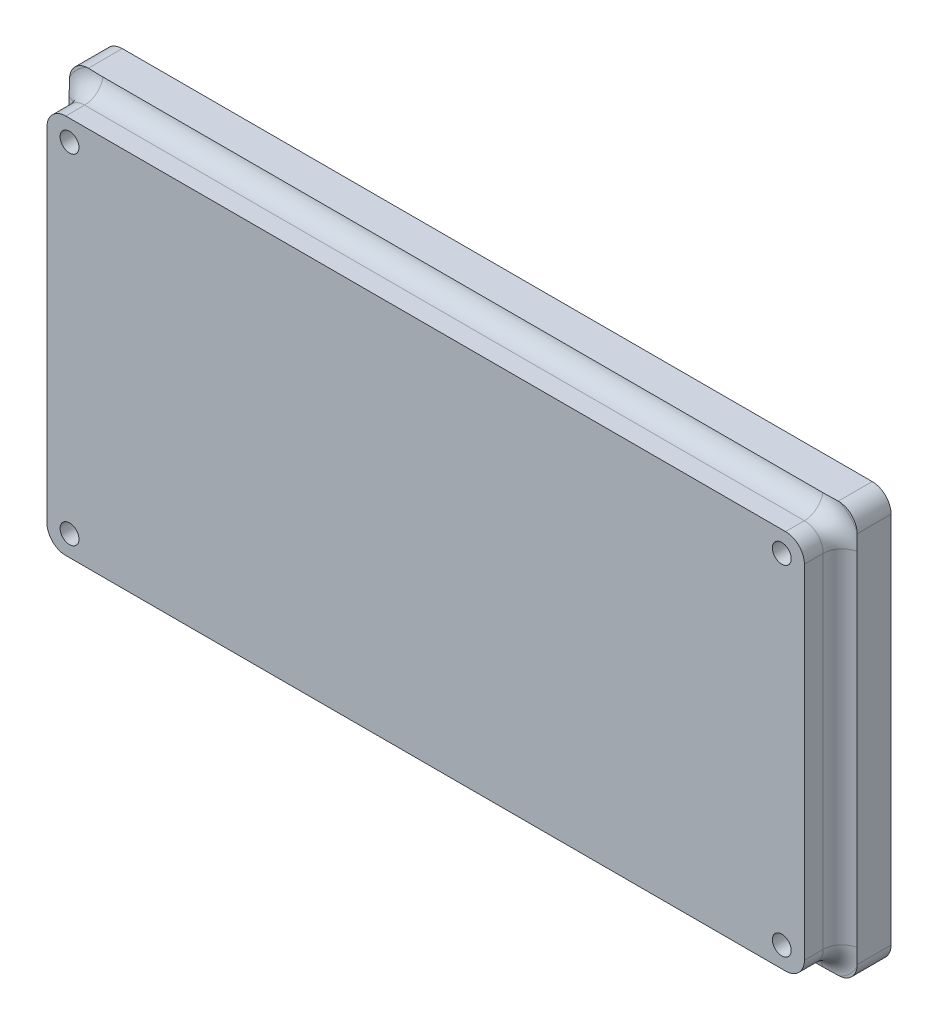
SolidWorks part; units mm, degrees
ref_plane "Plano frontal" through (0, 0, 0) normal (0, 0, 1) x (1, 0, 0)
ref_plane "Plano superior" through (0, 0, 0) normal (0, 1, 0) x (1, 0, 0)
ref_plane "Plano direito" through (0, 0, 0) normal (1, 0, 0) x (0, 0, -1)
sketch "Esboço1" plane through (0, 0, 0) normal (0, 0, 1) x (1, 0, 0)
  line L1 (-104.5, 54.5) -> (104.5, 54.5)
  line L2 (-104.5, 54.5) -> (-104.5, -54.5)
  line L3 (-104.5, -54.5) -> (104.5, -54.5)
  line L4 (104.5, 54.5) -> (104.5, -54.5)
  line L5 (-104.5, 54.5) -> (104.5, -54.5) construction
  line L6 (-104.5, -54.5) -> (104.5, 54.5) construction
  point P0 (0, 0)
  dimension "D1" = 209
  dimension "D2" = 109
extrude "Ressalto-extrusão2" add sketch "Esboço1" along normal blind 19
fillet "Filete2" radius 5 4 edges at (-104.5, 54.5, 9.5) (-104.5, -54.5, 9.5) (104.5, -54.5, 9.5) (104.5, 54.5, 9.5)
ref_plane "Plano Posterior" through (0, 0, 19) normal (0, 0, 1) x (1, 0, 0)
sketch "Esboço12" plane through (0, 0, 19) normal (0, 0, 1) x (1, 0, 0)
  line L1 (-100.5, 50.5) -> (100.5, 50.5)
  line L2 (-100.5, 50.5) -> (-100.5, -50.5)
  line L3 (-100.5, -50.5) -> (100.5, -50.5)
  line L4 (100.5, 50.5) -> (100.5, -50.5)
  line L5 (-100.5, 50.5) -> (100.5, -50.5) construction
  line L6 (-100.5, -50.5) -> (100.5, 50.5) construction
  point P0 (0, 0)
  dimension "D1" = 201
  dimension "D2" = 101
extrude "Corte-extrusão8" cut sketch "Esboço12" against normal blind 10 flip side to cut
fillet "Filete3" radius 5 4 edges at (100.5, -50.5, 14) (-100.5, -50.5, 14) (-100.5, 50.5, 14) (100.5, 50.5, 14)
fillet "Filete4" radius 5 4 edges at (-99.0355, 49.0355, 9) (99.0355, 49.0355, 9) (99.0355, -49.0355, 9) (-99.0355, -49.0355, 9)
sketch "Esboço14" plane through (0, 0, 0) normal (0, 0, 1) x (1, 0, 0)
  line L0 (97.5, -36.5) -> (90.5, -36.5)
  line L1 (97.5, 48.5) -> (-97.5, 48.5) construction
  line L2 (97.5, 48.5) -> (97.5, -48.5) construction
  line L3 (97.5, -48.5) -> (-97.5, -48.5) construction
  line L4 (-97.5, 48.5) -> (-97.5, -48.5) construction
  line L5 (97.5, 48.5) -> (-97.5, -48.5) construction
  line L6 (97.5, -48.5) -> (-97.5, 48.5) construction
  line L7 (85.5, -41.5) -> (85.5, -48.5)
  line L8 (0, 0) -> (-97.5, 0) construction
  line L9 (0, 0) -> (97.5, 0) construction
  line L10 (97.5, 36.5) -> (97.5, -36.5)
  line L11 (85.5, -48.5) -> (-85.5, -48.5)
  line L12 (85.5, 48.5) -> (-85.5, 48.5)
  line L13 (85.5, 41.5) -> (85.5, 48.5)
  line L14 (97.5, 36.5) -> (90.5, 36.5)
  line L15 (0, -48.5) -> (0, 48.5) construction
  line L16 (-85.5, 41.5) -> (-85.5, 48.5)
  line L17 (-97.5, 36.5) -> (-90.5, 36.5)
  line L18 (-97.5, 36.5) -> (-97.5, -36.5)
  line L19 (-97.5, -36.5) -> (-90.5, -36.5)
  line L20 (-85.5, -41.5) -> (-85.5, -48.5)
  arc A0 (85.5, -41.5) -> (90.5, -36.5) centre (90.5, -41.5) cw
  arc A1 (85.5, 41.5) -> (90.5, 36.5) centre (90.5, 41.5) ccw
  arc A2 (-85.5, 41.5) -> (-90.5, 36.5) centre (-90.5, 41.5) cw
  arc A3 (-85.5, -41.5) -> (-90.5, -36.5) centre (-90.5, -41.5) ccw
  point P0 (0, 0)
  point P11 (85.5, -36.5)
  dimension "D5" = 5
  dimension "D1" = 195
  dimension "D2" = 97
  dimension "D3" = 12
  dimension "D4" = 12
extrude "Corte-extrusão9" cut sketch "Esboço14" along normal blind 16
sketch "Esboço16" plane through (0, 0, 0) normal (0, 0, 1) x (1, 0, 0)
  line L0 (99.5, -38) -> (92.5, -38)
  line L1 (99.5, 50) -> (-99.5, 50) construction
  line L2 (99.5, 50) -> (99.5, -50) construction
  line L3 (99.5, -50) -> (-99.5, -50) construction
  line L4 (-99.5, 50) -> (-99.5, -50) construction
  line L5 (99.5, 50) -> (-99.5, -50) construction
  line L6 (99.5, -50) -> (-99.5, 50) construction
  line L7 (87.5, -43) -> (87.5, -50)
  line L8 (0, 0) -> (-99.5, 0) construction
  line L9 (0, 0) -> (99.5, 0) construction
  line L10 (99.5, 38) -> (99.5, -38)
  line L11 (87.5, -50) -> (-87.5, -50)
  line L12 (87.5, 50) -> (-87.5, 50)
  line L13 (87.5, 43) -> (87.5, 50)
  line L14 (99.5, 38) -> (92.5, 38)
  line L15 (0, -50) -> (0, 50) construction
  line L16 (-87.5, 43) -> (-87.5, 50)
  line L17 (-99.5, 38) -> (-92.5, 38)
  line L18 (-99.5, 38) -> (-99.5, -38)
  line L19 (-99.5, -38) -> (-92.5, -38)
  line L20 (-87.5, -43) -> (-87.5, -50)
  line L21 (0, 0) -> (-97.5, 0) construction
  line L22 (0, -48.5) -> (0, 48.5) construction
  line L24 (97.5, 52.5) -> (-97.5, 52.5)
  line L25 (102.5, 47.5) -> (102.5, -47.5)
  line L26 (97.5, -52.5) -> (-97.5, -52.5)
  line L27 (-102.5, 47.5) -> (-102.5, -47.5)
  line L28 (102.5, 52.5) -> (-102.5, -52.5) construction
  line L29 (102.5, -52.5) -> (-102.5, 52.5) construction
  arc A0 (87.5, -43) -> (92.5, -38) centre (92.5, -43) cw
  arc A1 (87.5, 43) -> (92.5, 38) centre (92.5, 43) ccw
  arc A2 (-87.5, 43) -> (-92.5, 38) centre (-92.5, 43) cw
  arc A3 (-87.5, -43) -> (-92.5, -38) centre (-92.5, -43) ccw
  arc A4 (-97.5, 52.5) -> (-102.5, 47.5) centre (-97.5, 47.5) ccw
  arc A5 (-102.5, -47.5) -> (-97.5, -52.5) centre (-97.5, -47.5) ccw
  arc A6 (97.5, -52.5) -> (102.5, -47.5) centre (97.5, -47.5) ccw
  arc A7 (97.5, 52.5) -> (102.5, 47.5) centre (97.5, 47.5) cw
  point P0 (0, 0)
  point P11 (87.5, -38)
  dimension "D5" = 5
  dimension "D8" = 5
  dimension "D1" = 199
  dimension "D2" = 100
  dimension "D3" = 12
  dimension "D4" = 12
  dimension "D6" = 205
  dimension "D7" = 105
extrude "Corte-extrusão10" cut sketch "Esboço16" along normal blind 3
sketch "Esboço17" plane through (0, 0, 0) normal (0, 0, 1) x (1, 0, 0)
  line L0 (102.5, -47.5) -> (102.5, 47.5) construction
  line L1 (96.5, 50) -> (90.5, 50)
  line L2 (99.5, 47) -> (99.5, 41)
  line L5 (99.5, 50) -> (90.5, 45.4774) construction
  line L6 (0, 0) -> (0, 26.6956) construction
  line L7 (-96.5, 50) -> (-90.5, 50)
  line L8 (99.5, 41) -> (93.5, 41)
  line L9 (90.5, 44) -> (90.5, 50)
  line L10 (-90.5, 44) -> (-90.5, 50)
  line L11 (-99.5, 41) -> (-93.5, 41)
  line L12 (99.5, 38) -> (92.5, 38) construction
  line L13 (87.5, 43) -> (87.5, 50) construction
  line L14 (0, 0) -> (-33.9733, 0) construction
  line L15 (-99.5, 47) -> (-99.5, 41)
  line L16 (-96.5, -50) -> (-90.5, -50)
  line L17 (-90.5, -44) -> (-90.5, -50)
  line L18 (-99.5, -41) -> (-93.5, -41)
  line L19 (-99.5, -47) -> (-99.5, -41)
  line L20 (96.5, -50) -> (90.5, -50)
  line L21 (90.5, -44) -> (90.5, -50)
  line L22 (99.5, -41) -> (93.5, -41)
  line L23 (99.5, -47) -> (99.5, -41)
  arc A0 (90.5, 44) -> (93.5, 41) centre (93.5, 44) ccw
  arc A1 (96.5, 50) -> (99.5, 47) centre (96.5, 47) cw
  arc A2 (-96.5, 50) -> (-99.5, 47) centre (-96.5, 47) ccw
  arc A3 (-90.5, 44) -> (-93.5, 41) centre (-93.5, 44) cw
  arc A4 (-90.5, -44) -> (-93.5, -41) centre (-93.5, -44) ccw
  arc A5 (-96.5, -50) -> (-99.5, -47) centre (-96.5, -47) cw
  arc A6 (96.5, -50) -> (99.5, -47) centre (96.5, -47) ccw
  arc A7 (90.5, -44) -> (93.5, -41) centre (93.5, -44) cw
  point P0 (0, 0)
  dimension "D5" = 3
  dimension "D6" = 3
  dimension "D1" = 3
  dimension "D3" = 3
  dimension "D4" = 3
extrude "Ressalto-extrusão3" add sketch "Esboço17" along normal blind 3
sketch "Esboço18" plane through (0, 0, 0) normal (0, 0, 1) x (1, 0, 0)
  line L0 (93.5, 41) -> (99.5, 41) construction
  line L2 (0, 0) -> (0, 72.5851) construction
  circle A0 centre (94.5, 45) radius 2.5
  dimension "D1" = 5
  dimension "D2" = 4
  dimension "D3" = 94.5
extrude "Corte-extrusão11" cut sketch "Esboço18" along normal through all
mirror "Espelhar1" about plane through (0, 0, 0) normal (0, 1, 0) of "Corte-extrusão11"
mirror "Espelhar2" about plane through (0, 0, 0) normal (1, 0, 0) of "Espelhar1"
